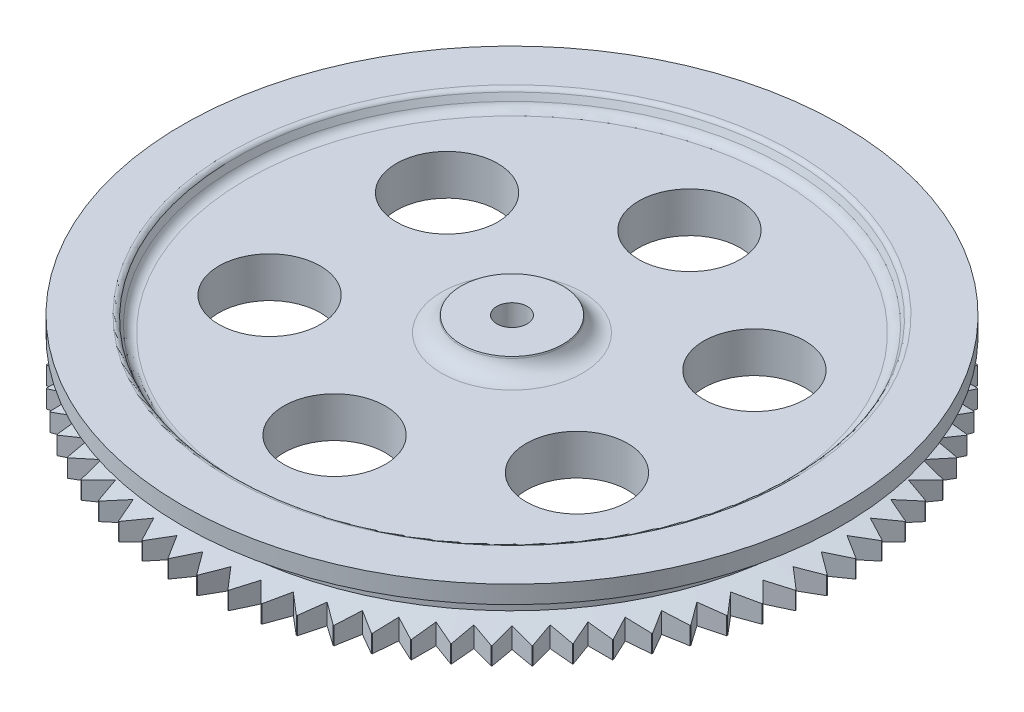
SolidWorks part; units mm, degrees
ref_plane "Спереди" through (0, 0, 0) normal (0, 0, 1) x (1, 0, 0)
ref_plane "Сверху" through (0, 0, 0) normal (0, 1, 0) x (1, 0, 0)
ref_plane "Справа" through (0, 0, 0) normal (1, 0, 0) x (0, 0, -1)
sketch "Эскиз1" plane through (0, 0, 0) normal (1, 0, 0) x (0, 0, -1)
  line L7 (0, 0) -> (0, 7)
  line L8 (0, 0) -> (0, -7)
  line L11 (-65, -7) -> (-55, -7)
  line L12 (-58, 0) -> (-58, 2.5)
  line L13 (-58, 0) -> (-58, -2.5)
  line L14 (-65, 7) -> (-65, 3.503)
  line L15 (-65, -7) -> (-65, -3.5)
  line L16 (-65, -3.5) -> (-58, -2.5)
  line L17 (-58, 2.5) -> (-65, 3.503)
  line L18 (0, -7) -> (-15, -7)
  line L19 (-65, 7) -> (-55, 7)
  line L20 (-51.6667, -4) -> (-20, -4)
  line L21 (-51.6667, -4) -> (-55, -7)
  line L22 (-20, -4) -> (-15, -7)
  line L23 (0, 7) -> (-10, 7)
  line L26 (-53.666, 4) -> (-55, 7)
  line L29 (-11, 4) -> (-10, 7)
  line L30 (-53.666, 4) -> (-11, 4)
  point P19 (0, 0)
  point P21 (0, 0)
  point P22 (0, 0)
  point P23 (0, 0)
  point P24 (0, 0)
  point P25 (0, 0)
  point P26 (0, 0)
  point P27 (0, 0)
  point P28 (0, 0)
  point P29 (0, 0)
revolve "Повернуть1" add sketch "Эскиз1" angle 360 about L8
ref_plane "Плоскость1" through (0, 7, 0) normal (0, 1, 0) x (1, 0, 0)
sketch "Эскиз2" plane through (0, 7, 0) normal (0, 1, 0) x (1, 0, 0)
  circle A0 centre (0, 0) radius 3
extrude "Вырез-Вытянуть1" cut sketch "Эскиз2" against normal through all
ref_plane "Плоскость2" through (0, -7, 0) normal (0, -1, 0) x (-1, 0, 0)
sketch "Эскиз3" plane through (0, -7, 0) normal (0, -1, 0) x (-1, 0, 0)
  line L5 (-6.5, 0) -> (-3.25, -5.6292)
  line L6 (-3.25, -5.6292) -> (3.25, -5.6292)
  line L7 (3.25, -5.6292) -> (6.5, 0)
  line L8 (6.5, 0) -> (3.25, 5.6292)
  line L9 (3.25, 5.6292) -> (-3.25, 5.6292)
  line L10 (-3.25, 5.6292) -> (-6.5, 0)
  circle A0 centre (0, 0) radius 5.6292 construction
extrude "Вырез-Вытянуть2" cut sketch "Эскиз3" against normal blind 5
sketch "Эскиз4" plane through (0, -7, 0) normal (0, -1, 0) x (-1, 0, 0)
  line L0 (-5.3165, -60.7679) -> (-8.4093, -64.4537)
  line L1 (-2.9107, -64.9348) -> (-5.3165, -60.7679)
  line L2 (0, -61) -> (-2.7598, -64.9414)
  line L4 (2.7598, -64.9414) -> (0, -61)
  line L5 (-10.5925, -60.0733) -> (-13.9948, -63.4755)
  line L6 (-8.5591, -64.434) -> (-10.5925, -60.0733)
  line L7 (-15.788, -58.9215) -> (-19.4738, -62.0143)
  line L8 (-14.1423, -63.4428) -> (-15.788, -58.9215)
  line L9 (-20.8632, -57.3212) -> (-24.8046, -60.081)
  line L10 (-19.6179, -61.9688) -> (-20.8632, -57.3212)
  line L11 (-25.7797, -55.2848) -> (-29.9466, -57.6905)
  line L12 (-24.9442, -60.0232) -> (-25.7797, -55.2848)
  line L13 (-30.5, -52.8275) -> (-34.8607, -54.861)
  line L14 (-30.0806, -57.6208) -> (-30.5, -52.8275)
  line L15 (-34.9882, -49.9683) -> (-39.5095, -51.6139)
  line L16 (-34.9882, -54.7798) -> (-34.9882, -49.9683)
  line L17 (-39.21, -46.7287) -> (-43.8576, -47.974)
  line L18 (-39.6294, -51.5219) -> (-39.21, -46.7287)
  line L19 (-43.1335, -43.1335) -> (-47.872, -43.969)
  line L20 (-43.969, -47.872) -> (-43.1335, -43.1335)
  line L21 (-46.7287, -39.21) -> (-51.5219, -39.6294)
  line L22 (-47.974, -43.8576) -> (-46.7287, -39.21)
  line L23 (-49.9683, -34.9882) -> (-54.7798, -34.9882)
  line L24 (-51.6139, -39.5095) -> (-49.9683, -34.9882)
  line L25 (-52.8275, -30.5) -> (-57.6208, -30.0806)
  line L26 (-54.861, -34.8607) -> (-52.8275, -30.5)
  line L27 (-55.2848, -25.7797) -> (-60.0232, -24.9442)
  line L28 (-57.6905, -29.9466) -> (-55.2848, -25.7797)
  line L29 (-57.3212, -20.8632) -> (-61.9688, -19.6179)
  line L30 (-60.081, -24.8046) -> (-57.3212, -20.8632)
  line L31 (-58.9215, -15.788) -> (-63.4428, -14.1423)
  line L32 (-62.0143, -19.4738) -> (-58.9215, -15.788)
  line L33 (-60.0733, -10.5925) -> (-64.434, -8.5591)
  line L34 (-63.4755, -13.9948) -> (-60.0733, -10.5925)
  line L35 (-60.7679, -5.3165) -> (-64.9348, -2.9107)
  line L36 (-64.4537, -8.4093) -> (-60.7679, -5.3165)
  line L37 (-61, 0) -> (-64.9414, 2.7598)
  line L38 (-64.9414, -2.7598) -> (-61, 0)
  line L39 (-60.7679, 5.3165) -> (-64.4537, 8.4093)
  line L40 (-64.9348, 2.9107) -> (-60.7679, 5.3165)
  line L41 (-60.0733, 10.5925) -> (-63.4755, 13.9948)
  line L42 (-64.434, 8.5591) -> (-60.0733, 10.5925)
  line L43 (-58.9215, 15.788) -> (-62.0143, 19.4738)
  line L44 (-63.4428, 14.1423) -> (-58.9215, 15.788)
  line L45 (-57.3212, 20.8632) -> (-60.081, 24.8046)
  line L46 (-61.9688, 19.6179) -> (-57.3212, 20.8632)
  line L47 (-55.2848, 25.7797) -> (-57.6905, 29.9466)
  line L48 (-60.0232, 24.9442) -> (-55.2848, 25.7797)
  line L49 (-52.8275, 30.5) -> (-54.861, 34.8607)
  line L50 (-57.6208, 30.0806) -> (-52.8275, 30.5)
  line L51 (-49.9683, 34.9882) -> (-51.6139, 39.5095)
  line L52 (-54.7798, 34.9882) -> (-49.9683, 34.9882)
  line L53 (-46.7287, 39.21) -> (-47.974, 43.8576)
  line L54 (-51.5219, 39.6294) -> (-46.7287, 39.21)
  line L55 (-43.1335, 43.1335) -> (-43.969, 47.872)
  line L56 (-47.872, 43.969) -> (-43.1335, 43.1335)
  line L57 (-39.21, 46.7287) -> (-39.6294, 51.5219)
  line L58 (-43.8576, 47.974) -> (-39.21, 46.7287)
  line L59 (-34.9882, 49.9683) -> (-34.9882, 54.7798)
  line L60 (-39.5095, 51.6139) -> (-34.9882, 49.9683)
  line L61 (-30.5, 52.8275) -> (-30.0806, 57.6208)
  line L62 (-34.8607, 54.861) -> (-30.5, 52.8275)
  line L63 (-25.7797, 55.2848) -> (-24.9442, 60.0232)
  line L64 (-29.9466, 57.6905) -> (-25.7797, 55.2848)
  line L65 (-20.8632, 57.3212) -> (-19.6179, 61.9688)
  line L66 (-24.8046, 60.081) -> (-20.8632, 57.3212)
  line L67 (-15.788, 58.9215) -> (-14.1423, 63.4428)
  line L68 (-19.4738, 62.0143) -> (-15.788, 58.9215)
  line L69 (-10.5925, 60.0733) -> (-8.5591, 64.434)
  line L70 (-13.9948, 63.4755) -> (-10.5925, 60.0733)
  line L71 (-5.3165, 60.7679) -> (-2.9107, 64.9348)
  line L72 (-8.4093, 64.4537) -> (-5.3165, 60.7679)
  line L73 (0, 61) -> (2.7598, 64.9414)
  line L74 (-2.7598, 64.9414) -> (0, 61)
  line L75 (5.3165, 60.7679) -> (8.4093, 64.4537)
  line L76 (2.9107, 64.9348) -> (5.3165, 60.7679)
  line L77 (10.5925, 60.0733) -> (13.9948, 63.4755)
  line L78 (8.5591, 64.434) -> (10.5925, 60.0733)
  line L79 (15.788, 58.9215) -> (19.4738, 62.0143)
  line L80 (14.1423, 63.4428) -> (15.788, 58.9215)
  line L81 (20.8632, 57.3212) -> (24.8046, 60.081)
  line L82 (19.6179, 61.9688) -> (20.8632, 57.3212)
  line L83 (25.7797, 55.2848) -> (29.9466, 57.6905)
  line L84 (24.9442, 60.0232) -> (25.7797, 55.2848)
  line L85 (30.5, 52.8275) -> (34.8607, 54.861)
  line L86 (30.0806, 57.6208) -> (30.5, 52.8275)
  line L87 (34.9882, 49.9683) -> (39.5095, 51.6139)
  line L88 (34.9882, 54.7798) -> (34.9882, 49.9683)
  line L89 (39.21, 46.7287) -> (43.8576, 47.974)
  line L90 (39.6294, 51.5219) -> (39.21, 46.7287)
  line L91 (43.1335, 43.1335) -> (47.872, 43.969)
  line L92 (43.969, 47.872) -> (43.1335, 43.1335)
  line L93 (46.7287, 39.21) -> (51.5219, 39.6294)
  line L94 (47.974, 43.8576) -> (46.7287, 39.21)
  line L95 (49.9683, 34.9882) -> (54.7798, 34.9882)
  line L96 (51.6139, 39.5095) -> (49.9683, 34.9882)
  line L97 (52.8275, 30.5) -> (57.6208, 30.0806)
  line L98 (54.861, 34.8607) -> (52.8275, 30.5)
  line L99 (55.2848, 25.7797) -> (60.0232, 24.9442)
  line L100 (57.6905, 29.9466) -> (55.2848, 25.7797)
  line L101 (57.3212, 20.8632) -> (61.9688, 19.6179)
  line L102 (60.081, 24.8046) -> (57.3212, 20.8632)
  line L103 (58.9215, 15.788) -> (63.4428, 14.1423)
  line L104 (62.0143, 19.4738) -> (58.9215, 15.788)
  line L105 (60.0733, 10.5925) -> (64.434, 8.5591)
  line L106 (63.4755, 13.9948) -> (60.0733, 10.5925)
  line L107 (60.7679, 5.3165) -> (64.9348, 2.9107)
  line L108 (64.4537, 8.4093) -> (60.7679, 5.3165)
  line L109 (61, 0) -> (64.9414, -2.7598)
  line L110 (64.9414, 2.7598) -> (61, 0)
  line L111 (60.7679, -5.3165) -> (64.4537, -8.4093)
  line L112 (64.9348, -2.9107) -> (60.7679, -5.3165)
  line L113 (60.0733, -10.5925) -> (63.4755, -13.9948)
  line L114 (64.434, -8.5591) -> (60.0733, -10.5925)
  line L115 (58.9215, -15.788) -> (62.0143, -19.4738)
  line L116 (63.4428, -14.1423) -> (58.9215, -15.788)
  line L117 (57.3212, -20.8632) -> (60.081, -24.8046)
  line L118 (61.9688, -19.6179) -> (57.3212, -20.8632)
  line L119 (55.2848, -25.7797) -> (57.6905, -29.9466)
  line L120 (60.0232, -24.9442) -> (55.2848, -25.7797)
  line L121 (52.8275, -30.5) -> (54.861, -34.8607)
  line L122 (57.6208, -30.0806) -> (52.8275, -30.5)
  line L123 (49.9683, -34.9882) -> (51.6139, -39.5095)
  line L124 (54.7798, -34.9882) -> (49.9683, -34.9882)
  line L125 (46.7287, -39.21) -> (47.974, -43.8576)
  line L126 (51.5219, -39.6294) -> (46.7287, -39.21)
  line L127 (43.1335, -43.1335) -> (43.969, -47.872)
  line L128 (47.872, -43.969) -> (43.1335, -43.1335)
  line L129 (39.21, -46.7287) -> (39.6294, -51.5219)
  line L130 (43.8576, -47.974) -> (39.21, -46.7287)
  line L131 (34.9882, -49.9683) -> (34.9882, -54.7798)
  line L132 (39.5095, -51.6139) -> (34.9882, -49.9683)
  line L133 (30.5, -52.8275) -> (30.0806, -57.6208)
  line L134 (34.8607, -54.861) -> (30.5, -52.8275)
  line L135 (25.7797, -55.2848) -> (24.9442, -60.0232)
  line L136 (29.9466, -57.6905) -> (25.7797, -55.2848)
  line L137 (20.8632, -57.3212) -> (19.6179, -61.9688)
  line L138 (24.8046, -60.081) -> (20.8632, -57.3212)
  line L139 (15.788, -58.9215) -> (14.1423, -63.4428)
  line L140 (19.4738, -62.0143) -> (15.788, -58.9215)
  line L141 (10.5925, -60.0733) -> (8.5591, -64.434)
  line L142 (13.9948, -63.4755) -> (10.5925, -60.0733)
  line L143 (5.3165, -60.7679) -> (2.9107, -64.9348)
  line L144 (8.4093, -64.4537) -> (5.3165, -60.7679)
  circle A0 centre (0, 0) radius 65
  point P222 (0, 0)
  dimension "D1" = 72
extrude "Вырез-Вытянуть6" cut sketch "Эскиз4" against normal blind 5 contours L17 A0 L18 | L13 A0 L14 | L9 A0 L10 | L5 A0 L6 | L2 A0 L4 | L141 A0 L142 | L137 A0 L138 | L133 A0 L134 | L129 A0 L130 | L125 A0 L126 | L121 A0 L122 | L117 A0 L118 region at (11.0533, -7, 62.6866) region at (0, -7, 63.6536) region at (21.7708, -7, 59.8148) region at (-11.0533, -7, 62.6866) region at (31.8268, -7, 55.1256) region at (-21.7708, -7, 59.8148) region at (40.9157, -7, 48.7615) region at (-31.8268, -7, 55.1256) region at (-40.9157, -7, 48.7615) region at (-48.7615, -7, 40.9157) region at (-55.1256, -7, 31.8268) region at (-59.8148, -7, 21.7708)
extrude "Вырез-Вытянуть7" cut sketch "Эскиз4<6>" against normal blind 5 contours L113 A0 L114 | L109 A0 L110 | L105 A0 L106 | L101 A0 L102 | L97 A0 L98 | L93 A0 L94 | L89 A0 L90 | L85 A0 L86 | L81 A0 L82 | L77 A0 L78 | L73 A0 L74 | L69 A0 L70 region at (-62.6866, -7, 11.0533) region at (-63.6536, -7, 0) region at (-62.6866, -7, -11.0533) region at (-59.8148, -7, -21.7708) region at (-55.1256, -7, -31.8268) region at (-48.7615, -7, -40.9157) region at (-40.9157, -7, -48.7615) region at (-31.8268, -7, -55.1256) region at (11.0533, -7, -62.6866) region at (-21.7708, -7, -59.8148) region at (0, -7, -63.6536) region at (-11.0533, -7, -62.6866)
sketch "Эскиз4<6>" plane through (0, -7, 0) normal (0, -1, 0) x (-1, 0, 0) same geometry as "Эскиз4"
extrude "Вырез-Вытянуть8" cut sketch "Эскиз4<7>" against normal blind 5 contours L65 A0 L66 | L61 A0 L62 | L57 A0 L58 | L53 A0 L54 | L49 A0 L50 | L45 A0 L46 | L41 A0 L42 | L37 A0 L38 | L33 A0 L34 | L29 A0 L30 | L25 A0 L26 | L21 A0 L22 region at (48.7615, -7, 40.9157) region at (55.1256, -7, 31.8268) region at (59.8148, -7, 21.7708) region at (62.6866, -7, 11.0533) region at (63.6536, -7, 0) region at (62.6866, -7, -11.0533) region at (59.8148, -7, -21.7708) region at (55.1256, -7, -31.8268) region at (48.7615, -7, -40.9157) region at (40.9157, -7, -48.7615) region at (31.8268, -7, -55.1256) region at (21.7708, -7, -59.8148)
sketch "Эскиз4<7>" plane through (0, -7, 0) normal (0, -1, 0) x (-1, 0, 0) same geometry as "Эскиз4"
extrude "Вырез-Вытянуть9" cut sketch "Эскиз4<8>" against normal blind 5 contours L0 A0 L1 | L143 A0 L144 | L139 A0 L140 | L135 A0 L136 | L131 A0 L132 | L127 A0 L128 | L123 A0 L124 | L119 A0 L120 | L115 A0 L116 | L111 A0 L112 | L107 A0 L108 | L103 A0 L104 region at (5.5478, -7, 63.4114) region at (-5.5478, -7, 63.4114) region at (-16.4748, -7, 61.4846) region at (-26.9012, -7, 57.6897) region at (-36.5102, -7, 52.142) region at (-45.0099, -7, 45.0099) region at (-52.142, -7, 36.5102) region at (-57.6897, -7, 26.9012) region at (-61.4846, -7, 16.4748) region at (-63.4114, -7, 5.5478) region at (-63.4114, -7, -5.5478) region at (-61.4846, -7, -16.4748)
sketch "Эскиз4<8>" plane through (0, -7, 0) normal (0, -1, 0) x (-1, 0, 0) same geometry as "Эскиз4"
extrude "Вырез-Вытянуть10" cut sketch "Эскиз4<9>" against normal blind 5 contours L99 A0 L100 | L95 A0 L96 | L91 A0 L92 | L87 A0 L88 | L83 A0 L84 | L79 A0 L80 | L75 A0 L76 | L71 A0 L72 | L67 A0 L68 | L63 A0 L64 | L59 A0 L60 | L55 A0 L56 region at (-57.6897, -7, -26.9012) region at (45.0099, -7, -45.0099) region at (-52.142, -7, -36.5102) region at (36.5102, -7, -52.142) region at (-45.0099, -7, -45.0099) region at (26.9012, -7, -57.6897) region at (-36.5102, -7, -52.142) region at (16.4748, -7, -61.4846) region at (-26.9012, -7, -57.6897) region at (5.5478, -7, -63.4114) region at (-16.4748, -7, -61.4846) region at (-5.5478, -7, -63.4114)
sketch "Эскиз4<9>" plane through (0, -7, 0) normal (0, -1, 0) x (-1, 0, 0) same geometry as "Эскиз4"
extrude "Вырез-Вытянуть11" cut sketch "Эскиз4<10>" against normal blind 5 contours L51 A0 L52 | L47 A0 L48 | L43 A0 L44 | L39 A0 L40 | L35 A0 L36 | L31 A0 L32 | L27 A0 L28 | L23 A0 L24 | L19 A0 L20 | L15 A0 L16 | L11 A0 L12 | L7 A0 L8 region at (16.4748, -7, 61.4846) region at (26.9012, -7, 57.6897) region at (36.5102, -7, 52.142) region at (45.0099, -7, 45.0099) region at (52.142, -7, 36.5102) region at (57.6897, -7, 26.9012) region at (61.4846, -7, 16.4748) region at (63.4114, -7, 5.5478) region at (63.4114, -7, -5.5478) region at (61.4846, -7, -16.4748) region at (57.6897, -7, -26.9012) region at (52.142, -7, -36.5102)
sketch "Эскиз4<10>" plane through (0, -7, 0) normal (0, -1, 0) x (-1, 0, 0) same geometry as "Эскиз4"
sketch "Эскиз5" plane through (0, -7, 0) normal (0, -1, 0) x (-1, 0, 0)
  circle A0 centre (0, 35) radius 10
  circle A1 centre (30.3109, 17.5) radius 10
  circle A2 centre (30.3109, -17.5) radius 10
  circle A3 centre (0, -35) radius 10
  circle A4 centre (-30.3109, -17.5) radius 10
  circle A5 centre (-30.3109, 17.5) radius 10
  point P16 (0, 0)
  dimension "D1" = 6
extrude "Вырез-Вытянуть12" cut sketch "Эскиз5" against normal through all
fillet "Скругление1" radius 2 1 edges at (0, 4, 53.666)
fillet "Скругление2" radius 1 1 edges at (0, 7, 55)
fillet "Скругление3" radius 4 1 edges at (0, 4, 11)
fillet "Скругление4" radius 6 1 edges at (0, -4, 20)
fillet "Скругление5" radius 3 1 edges at (0, -4, 51.6667)
fillet "Скругление6" radius 1 1 edges at (0, -7, 55)
